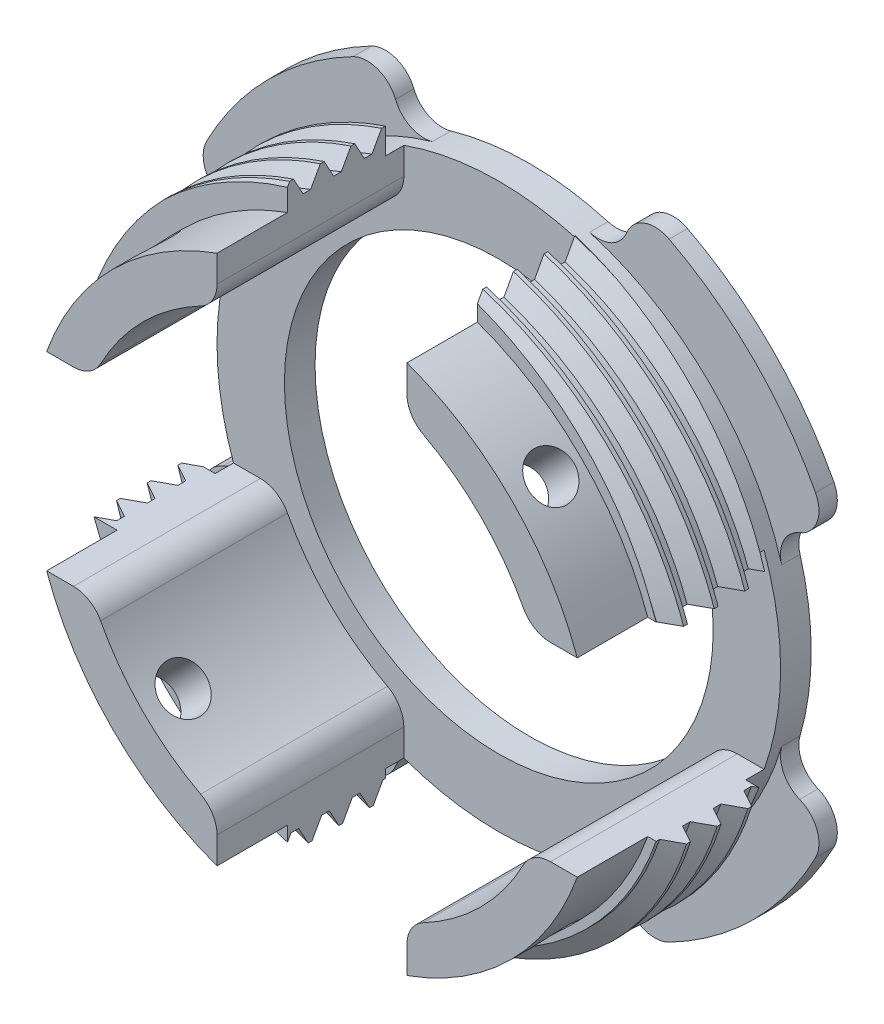
SolidWorks part; units mm, degrees
material "201 Annealed Stainless Steel (SS)"
ref_plane "前视基准面" through (0, 0, 0) normal (0, 0, 1) x (1, 0, 0)
ref_plane "上视基准面" through (0, 0, 0) normal (0, 1, 0) x (1, 0, 0)
ref_plane "右视基准面" through (0, 0, 0) normal (1, 0, 0) x (0, 0, -1)
other "Configuration Table"
sketch "Sketch1" plane through (0, 0, 0) normal (0, 0, 1) x (1, 0, 0)
  circle A0 centre (0, 0) radius 3.9
  circle A1 centre (0, 0) radius 4.6
  dimension "D1" = 7.8
  dimension "D2" = 9.2
extrude "Boss-Extrude1" add sketch "Sketch1" along normal blind 0.5
sketch "Sketch2" plane through (0, 0, 0.5) normal (0, 0, 1) x (1, 0, 0)
  line L0 (4.331, 1.55) -> (3.5788, 1.55)
  line L1 (-4.331, 1.55) -> (-3.5788, 1.55)
  line L5 (1.55, 4.331) -> (1.55, 3.5788)
  line L6 (1.55, -4.331) -> (1.55, -3.5788)
  line L8 (-1.55, 4.331) -> (-1.55, 3.5788)
  line L11 (4.331, -1.55) -> (3.5788, -1.55)
  line L12 (-4.331, -1.55) -> (-3.5788, -1.55)
  line L13 (-1.55, -4.331) -> (-1.55, -3.5788)
  arc A0 (-3.5788, 1.55) -> (-1.55, 3.5788) centre (0, 0) cw
  arc A1 (-1.55, 4.331) -> (-4.331, 1.55) centre (0, 0) ccw
  arc A2 (1.55, 3.5788) -> (3.5788, 1.55) centre (0, 0) cw
  arc A3 (4.331, 1.55) -> (1.55, 4.331) centre (0, 0) ccw
  arc A4 (3.5788, -1.55) -> (1.55, -3.5788) centre (0, 0) cw
  arc A5 (1.55, -4.331) -> (4.331, -1.55) centre (0, 0) ccw
  arc A6 (-1.55, -3.5788) -> (-3.5788, -1.55) centre (0, 0) cw
  arc A7 (-4.331, -1.55) -> (-1.55, -4.331) centre (0, 0) ccw
  circle A8 centre (0, 0) radius 3.9 construction
  circle A9 centre (0, 0) radius 4.6 construction
  point P0 (0, 0)
  point P6 (0, 0)
  point P25 (0, 0)
  dimension "D1" = 4
  dimension "D2" = 1.55
  dimension "D4" = 1.55
  dimension "D5" = 1.55
  dimension "D6" = 1.55
extrude "Boss-Extrude2" add sketch "Sketch2" along normal blind 3.05
sketch "Sketch3" plane through (0, 0, 0.5) normal (0, 0, 1) x (1, 0, 0)
  line L0 (0, 0) -> (3.2527, 3.2527) construction
  line L1 (0, 0) -> (3.2527, -3.2527) construction
  arc A0 (4.331, 1.55) -> (1.55, 4.331) centre (0, 0) ccw construction
  arc A1 (1.55, -4.331) -> (4.331, -1.55) centre (0, 0) ccw construction
ref_plane "Plane1" through (-3.2527, 3.2527, 0) normal (-0.7071, 0.7071, 0) x (0.7071, 0.7071, 0)
ref_plane "Plane2" through (3.2527, 3.2527, 0) normal (0.7071, 0.7071, 0) x (0, 0, -1)
sketch "Sketch5" plane through (3.2527, 3.2527, 0) normal (0.7071, 0.7071, 0) x (0, 0, -1)
  line L0 (0, -4.6) -> (0, 4.6) construction
  circle A0 centre (-2.9, 0) radius 0.5
  point P0 (-2.9, 0)
  dimension "D1" = 1
  dimension "D2" = 2.9
hole_wizard "M1x0.25 螺纹孔1" positions "Sketch5" profile "草图5" tap size "M1x0.25" standard "JIS"
cosmetic thread "孔螺纹线1" parameters "D1"=2.5, "D2"=1
sketch "草图5" plane through (3.2527, 3.2527, 2.9) normal (0, 0, 1) x (-0.7071, 0.7071, 0)
  line L0 (0, 0) -> (0, 3.4753)
  line L1 (0, 3.4753) -> (0.375, 3.25)
  line L2 (0.375, 3.25) -> (0.375, 0)
  line L5 (0.375, 0) -> (0, 0)
  line L10 (0, 3.4753) -> (-0.375, 3.25) construction
  line L11 (0, -6.35) -> (0, 107.95) construction
  dimension "螺纹孔钻头直径" = 0.75
  dimension "螺纹孔钻头深度" = 3.25
  dimension "导头角度" = 118
fillet "圆角1" radius 0.5 8 edges at (3.5788, 1.55, 2.025) (1.55, 3.5788, 2.025) (3.5788, -1.55, 2.025) (1.55, -3.5788, 2.025) (-1.55, -3.5788, 2.025) (-3.5788, -1.55, 2.025) (-3.5788, 1.55, 2.025) (-1.55, 3.5788, 2.025)
sketch "草图1" plane through (0, 0, 0) normal (0, 0, 1) x (1, 0, 0)
  line L0 (-1.55, -4.0109) -> (-1.55, -4.7537)
  line L1 (0, 0) -> (0, 1.2915) construction
  line L2 (1.55, -4.0109) -> (1.55, -4.7537)
  line L3 (-1.55, -4.331) -> (-1.55, -3.8933) construction
  line L4 (-4.0109, 1.55) -> (-4.7537, 1.55)
  line L5 (-4.0109, -1.55) -> (-4.7537, -1.55)
  line L6 (1.55, 4.0109) -> (1.55, 4.7537)
  line L7 (-1.55, 4.0109) -> (-1.55, 4.7537)
  line L8 (4.0109, -1.55) -> (4.7537, -1.55)
  line L9 (4.0109, 1.55) -> (4.7537, 1.55)
  arc A0 (-4.7537, -1.55) -> (-1.55, -4.7537) centre (0, 0) ccw
  arc A1 (-4.0109, -1.55) -> (-1.55, -4.0109) centre (0, 0) ccw
  arc A2 (4.7537, 1.55) -> (1.55, 4.7537) centre (0, 0) ccw
  arc A3 (4.0109, 1.55) -> (1.55, 4.0109) centre (0, 0) ccw
  arc A4 (1.55, -4.0109) -> (4.0109, -1.55) centre (0, 0) ccw
  arc A5 (1.55, -4.7537) -> (4.7537, -1.55) centre (0, 0) ccw
  arc A6 (-1.55, 4.7537) -> (-4.7537, 1.55) centre (0, 0) ccw
  arc A7 (-1.55, 4.0109) -> (-4.0109, 1.55) centre (0, 0) ccw
  dimension "D1" = 10
  dimension "D2" = 8.6
  dimension "D3" = 4
extrude "凸台-拉伸1" add sketch "草图1" along normal blind 2.4
thread "螺纹线1" pitch 0.5 method cut trim with start face yes trim with end face yes profile "螺纹线轮廓1" start angle 0, offset 1, length 0, pitch 0.5, diameter 10
ref_plane "基准面1" through (-5, 0, 3.4) normal (0, -1, 0) x (-1, 0, 0)
sketch "螺纹线轮廓1" plane through (-5, 0, 3.4) normal (0, -1, 0) x (-1, 0, 0)
  line L0 (0, 0) -> (0, 0.5) construction
  line L11 (0, 0) -> (0, 0.4375)
  line L12 (0, 0.4375) -> (-0.2706, 0.2812)
  line L13 (-0.2706, 0.2812) -> (-0.2706, 0.1562)
  line L15 (-0.2706, 0.1562) -> (0, 0)
  line L17 (-0.2706, 0.2187) -> (0, 0.2187) construction
  point P2 (0, 0)
  dimension "Pitch" = 0.5
  dimension "Profile_Angle" = 60
  dimension "Profile_Land" = 0.125
  dimension "Profile_Height" = 0.2706
other "移动面1" [suppressed] flip direction yes offset 0.2 parameters "D1"=0.2
sketch "草图6" plane through (0, 0, 0) normal (0, 1, 0) x (1, 0, 0)
  line L0 (0, 0) -> (0, -3.7729) construction
pattern_circular "阵列(圆周)1" count 4 over 360 about axis through (0, 0, 0) along (0, 0, 1) of "M1x0.25 螺纹孔1" reverse direction yes
sketch "草图9" plane through (0, 0, 0) normal (0, 0, -1) x (-1, 0, 0)
  circle A0 centre (0, 0) radius 3.9
  circle A1 centre (0, 0) radius 3.5
  circle A2 centre (0, 0) radius 3.9 construction
  dimension "D1" = 7
extrude "凸台-拉伸2" add sketch "草图9" against normal up to surface (0.5 mm away) up to face at (-3.999, 0, 0.5)
sketch "草图10" plane through (0, 0, 0) normal (0, 0, -1) x (-1, 0, 0)
  circle A0 centre (0, 0) radius 4.7294
  arc A3 (-1.55, 4.4682) -> (-4.4682, 1.55) centre (0, 0) ccw construction
  circle A4 centre (0, 0) radius 3.5
  dimension "D1" = 7
extrude "凸台-拉伸3" [suppressed] add sketch "草图10" along normal blind 0.5
sketch "草图11" plane through (0, 0, 0) normal (0, 0, -1) x (-1, 0, 0)
  circle A0 centre (0, 0) radius 4.6
  dimension "D1" = 9.2
extrude "切除-拉伸1" cut sketch "草图11" against normal offset from surface (0.8 mm away) 0.3 flip side to cut up to face at (0, 0, 0.5) offset beyond the face yes
sketch "草图12" plane through (0, 0, 0) normal (0, 0, -1) x (-1, 0, 0)
  line L0 (-1.85, -4.2116) -> (-1.85, -5.2856)
  line L2 (-4.2116, -1.85) -> (-5.2856, -1.85)
  line L7 (-4.2116, 1.85) -> (-5.2856, 1.85)
  line L8 (-1.85, 4.2116) -> (-1.85, 5.2856)
  line L9 (1.85, 4.2116) -> (1.85, 5.2856)
  line L10 (4.2116, 1.85) -> (5.2856, 1.85)
  line L11 (4.2116, -1.85) -> (5.2856, -1.85)
  line L12 (1.85, -4.2116) -> (1.85, -5.2856)
  arc A0 (-4.2116, -1.85) -> (-1.85, -4.2116) centre (0, 0) ccw
  arc A2 (-4.7537, -1.55) -> (-1.55, -4.7537) centre (0, 0) ccw construction
  arc A3 (-1.85, -5.2856) -> (-5.2856, -1.85) centre (0, 0) cw
  circle A4 centre (0, 0) radius 4.6 construction
  arc A6 (-1.85, 4.2116) -> (-4.2116, 1.85) centre (0, 0) ccw
  arc A7 (-5.2856, 1.85) -> (-1.85, 5.2856) centre (0, 0) cw
  arc A8 (4.2116, 1.85) -> (1.85, 4.2116) centre (0, 0) ccw
  arc A9 (1.85, 5.2856) -> (5.2856, 1.85) centre (0, 0) cw
  arc A10 (1.85, -4.2116) -> (4.2116, -1.85) centre (0, 0) ccw
  arc A11 (5.2856, -1.85) -> (1.85, -5.2856) centre (0, 0) cw
  dimension "D1" = 1
  dimension "D3" = 3.7
  dimension "D2" = 4
extrude "凸台-拉伸4" add sketch "草图12" against normal blind 0.3
fillet "圆角3" radius 0.5 8 edges at (-1.85, 5.2856, 0.15) (-5.2856, 1.85, 0.15) (-5.2856, -1.85, 0.15) (-1.85, -5.2856, 0.15) (1.85, -5.2856, 0.15) (5.2856, -1.85, 0.15) (5.2856, 1.85, 0.15) (1.85, 5.2856, 0.15)
fillet "圆角4" radius 0.5 8 edges at (-1.85, -4.2116, 0.15) (-4.2116, -1.85, 0.15) (-4.2116, 1.85, 0.15) (-1.85, 4.2116, 0.15) (1.85, 4.2116, 0.15) (4.2116, 1.85, 0.15) (4.2116, -1.85, 0.15) (1.85, -4.2116, 0.15)
equation "\"1.9、\"=1.7"
